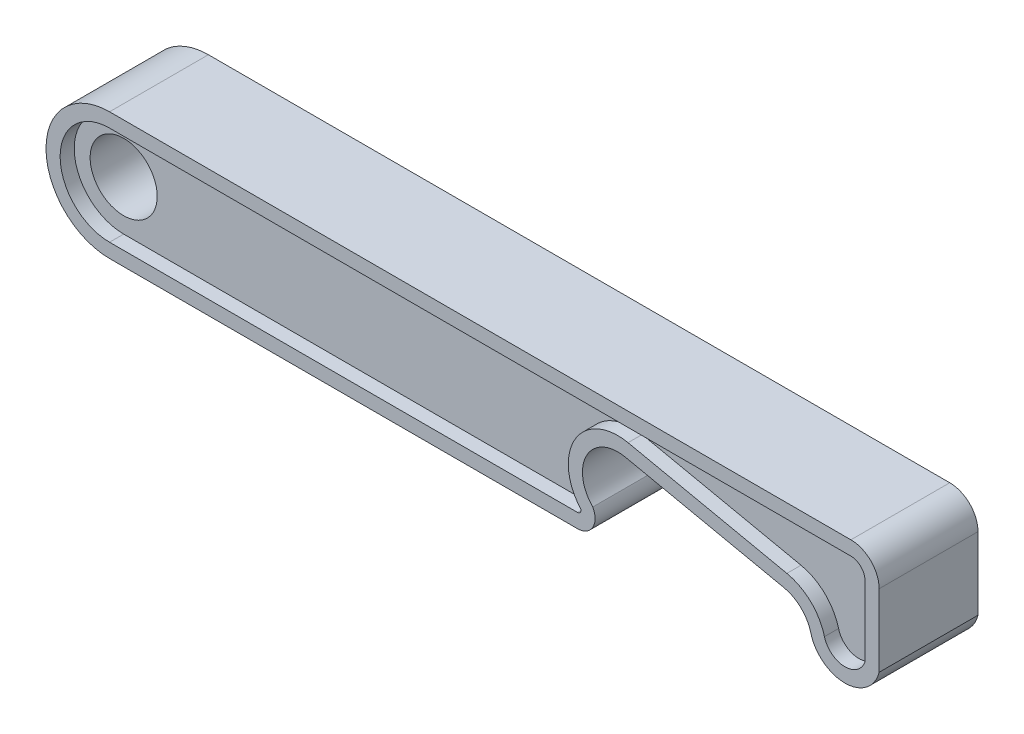
SolidWorks part; units mm, degrees
material "AISI 1020"
ref_plane "Front Plane" through (0, 0, 0) normal (0, 0, 1) x (1, 0, 0)
ref_plane "Top Plane" through (0, 0, 0) normal (0, 1, 0) x (1, 0, 0)
ref_plane "Right Plane" through (0, 0, 0) normal (1, 0, 0) x (0, 0, -1)
sketch "Sketch1" plane through (0, 0, 0) normal (0, 0, 1) x (1, 0, 0)
  line L0 (0, -9) -> (66.2727, -9)
  line L1 (0, 9) -> (105, 9)
  line L2 (73.0159, 3.1733) -> (95.5159, -1.6093)
  line L3 (109, -5.25) -> (109, 5)
  line L4 (-9, 0) -> (9, 0) construction
  circle A0 centre (0, 0) radius 4.75
  circle A1 centre (0, 0) radius 9
  arc A3 (73.0159, 3.1733) -> (68.4378, -5.25) centre (71.9763, -1.7175) ccw
  arc A4 (66.2727, -9) -> (68.4378, -5.25) centre (66.2727, -6.5) ccw
  arc A6 (95.5159, -1.6093) -> (99.3175, -5.25) centre (94.4763, -6.5) cw
  arc A7 (99.3175, -5.25) -> (109, -5.25) centre (104.1588, -4) ccw
  arc A8 (105, 9) -> (109, 5) centre (105, 5) cw
  point P19 (76.4814, -4.9244)
  point P22 (53.3641, -4.924)
  point P23 (0, 0)
  point P24 (50.5689, -4)
  point P25 (49.2435, -9)
  point P26 (50.8737, -4.5755)
  point P27 (50.676, -4.2684)
  point P28 (50.7537, -4.3951)
  point P29 (0, 0)
  point P30 (49.4049, -9)
  point P31 (51.4158, -5.25)
  point P32 (0, 0)
  dimension "D2" = 9.5
  dimension "D4" = 5
  dimension "D6" = 5
  dimension "D7" = 2.5
  dimension "D9" = 5
  dimension "D10" = 4
  dimension "D1" = 18
  dimension "D3" = 118
  dimension "D5" = 12
  dimension "D8" = 22.5
  dimension "D11" = 35.7429
  dimension "D12" = 12.473
extrude "Boss-Extrude1" add sketch "Sketch1" along normal mid plane 10 contours A8 L1 A1 L0 A4 A3 L2 A6 A7 L3 | L4 A1 A0 | A1 L4 A0 region at (52.8131, 0.8241, 0) region at (-6.2217, -6.2217, 0) region at (-6.2217, 6.2217, 0)
sketch "Sketch2" plane through (0, 0, 5) normal (0, 0, 1) x (1, 0, 0)
  line L8 (105, 9) -> (0, 9)
  line L9 (0, -9) -> (66.2727, -9)
  line L10 (73.0159, 3.1733) -> (95.5159, -1.6093)
  line L11 (109, -5.25) -> (109, 5)
  line L12 (105, 9) -> (0, 9)
  line L13 (0, -9) -> (66.2727, -9)
  line L14 (73.0159, 3.1733) -> (95.5159, -1.6093)
  line L15 (109, -5.25) -> (109, 5)
  line L20 (105, 7) -> (0, 7)
  line L21 (0, -7) -> (66.2727, -7)
  line L22 (73.4317, 5.1296) -> (95.9317, 0.347)
  line L23 (107, -4.963) -> (107, 5)
  line L24 (105, 7) -> (0, 7)
  line L25 (0, -7) -> (66.2727, -7)
  line L26 (73.4317, 5.1296) -> (95.9317, 0.347)
  line L27 (107, -4.963) -> (107, 5)
  arc A12 (109, 5) -> (105, 9) centre (105, 5) ccw
  arc A13 (0, 9) -> (0, -9) centre (0, 0) ccw
  arc A14 (66.2727, -9) -> (68.4378, -5.25) centre (66.2727, -6.5) ccw
  arc A15 (73.0159, 3.1733) -> (68.4378, -5.25) centre (71.9763, -1.7175) ccw
  arc A16 (99.3175, -5.25) -> (95.5159, -1.6093) centre (94.4763, -6.5) ccw
  arc A17 (99.3175, -5.25) -> (109, -5.25) centre (104.1588, -4) ccw
  arc A18 (109, 5) -> (105, 9) centre (105, 5) ccw
  arc A19 (0, 9) -> (0, -9) centre (0, 0) ccw
  arc A20 (66.2727, -9) -> (68.4378, -5.25) centre (66.2727, -6.5) ccw
  arc A21 (73.0159, 3.1733) -> (68.4378, -5.25) centre (71.9763, -1.7175) ccw
  arc A22 (99.3175, -5.25) -> (95.5159, -1.6093) centre (94.4763, -6.5) ccw
  arc A23 (99.3175, -5.25) -> (109, -5.25) centre (104.1588, -4) ccw
  arc A30 (107, 5) -> (105, 7) centre (105, 5) ccw
  arc A31 (0, 7) -> (0, -7) centre (0, 0) ccw
  arc A32 (66.2727, -7) -> (66.7592, -6.3846) centre (66.2727, -6.5) ccw
  arc A33 (73.4317, 5.1296) -> (66.7592, -6.3846) centre (71.9763, -1.7175) ccw
  arc A34 (101.254, -4.75) -> (95.9317, 0.347) centre (94.4763, -6.5) ccw
  arc A35 (101.254, -4.75) -> (107, -4.963) centre (104.1588, -4) ccw
  arc A36 (107, 5) -> (105, 7) centre (105, 5) ccw
  arc A37 (0, 7) -> (0, -7) centre (0, 0) ccw
  arc A38 (66.2727, -7) -> (66.7592, -6.3846) centre (66.2727, -6.5) ccw
  arc A39 (73.4317, 5.1296) -> (66.7592, -6.3846) centre (71.9763, -1.7175) ccw
  arc A40 (101.254, -4.75) -> (95.9317, 0.347) centre (94.4763, -6.5) ccw
  arc A41 (101.254, -4.75) -> (107, -4.963) centre (104.1588, -4) ccw
  dimension "D2" = 2
extrude "Boss-Extrude2" add sketch "Sketch2" against normal offset from surface (14 mm away) 2 from offset 2 up to face at (4.75, 0, -5) offset beyond the face yes
equation "\"A\" = 118"
equation "\"B\" = 14"
equation "\"C\"= 2"
equation "\"D3@Sketch1\"=\"A\""
equation "\"D1@Boss-Extrude1\"=\"B\"-2*\"C\""
equation "\"D2@Sketch2\"=\"C\""
equation "\"D1@Boss-Extrude2\"=\"C\""
equation "\"D19@Boss-Extrude2\"=\"C\""
